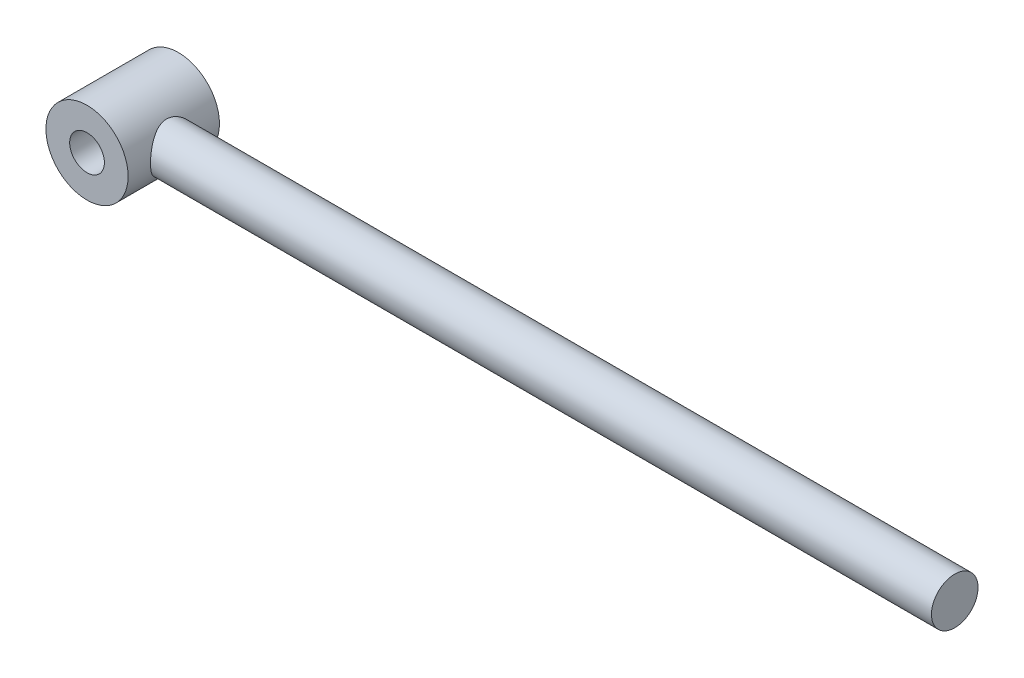
SolidWorks part; units mm, degrees
ref_plane "Front Plane" through (0, 0, 0) normal (0, 0, 1) x (1, 0, 0)
ref_plane "Top Plane" through (0, 0, 0) normal (0, 1, 0) x (1, 0, 0)
ref_plane "Right Plane" through (0, 0, 0) normal (1, 0, 0) x (0, 0, -1)
sketch "Sketch1" plane through (0, 0, 0) normal (0, 0, 1) x (1, 0, 0)
  line L1 (0, 0) -> (1800, 0)
  line L2 (0, 0) -> (0, 51)
  line L3 (0, 51) -> (1800, 51)
  line L4 (1800, 0) -> (1800, 51)
  dimension "D1" = 51
  dimension "D2" = 1800
revolve "Revolve1" add sketch "Sketch1" angle 360 about L1
sketch "Sketch2" plane through (0, 0, 0) normal (0, 0, 1) x (1, 0, 0)
  circle A0 centre (0, 0) radius 38
  circle A1 centre (0, 0) radius 90
  dimension "D1" = 180
  dimension "D2" = 76
extrude "Boss-Extrude1" add sketch "Sketch2" along normal mid plane 200
extrude "Cut-Extrude1" cut sketch "Sketch2<2>" against normal through all both and the other way through all contours A0 region at (0, 0, 0)
sketch "Sketch2<2>" plane through (0, 0, 0) normal (0, 0, 1) x (1, 0, 0) same geometry as "Sketch2"
